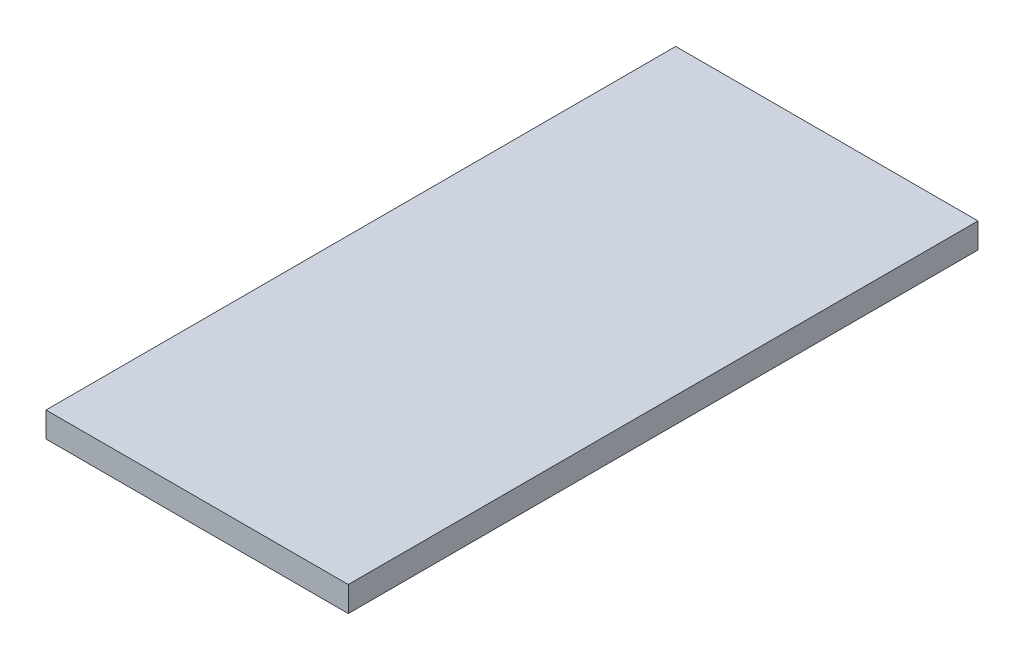
SolidWorks part; units mm, degrees
ref_plane "前视基准面" through (0, 0, 0) normal (0, 0, 1) x (1, 0, 0)
ref_plane "上视基准面" through (0, 0, 0) normal (0, 1, 0) x (1, 0, 0)
ref_plane "右视基准面" through (0, 0, 0) normal (1, 0, 0) x (0, 0, -1)
sketch "草图1" plane through (0, 0, 0) normal (0, 1, 0) x (1, 0, 0)
  line L1 (12, -25) -> (-12, -25)
  line L2 (12, -25) -> (12, 25)
  line L3 (12, 25) -> (-12, 25)
  line L4 (-12, -25) -> (-12, 25)
  line L5 (12, -25) -> (-12, 25) construction
  line L6 (12, 25) -> (-12, -25) construction
  point P1 (0, 0)
  point P6 (0, 0)
  point P7 (0, 0)
extrude "凸台-拉伸1" add sketch "草图1" along normal blind 2
